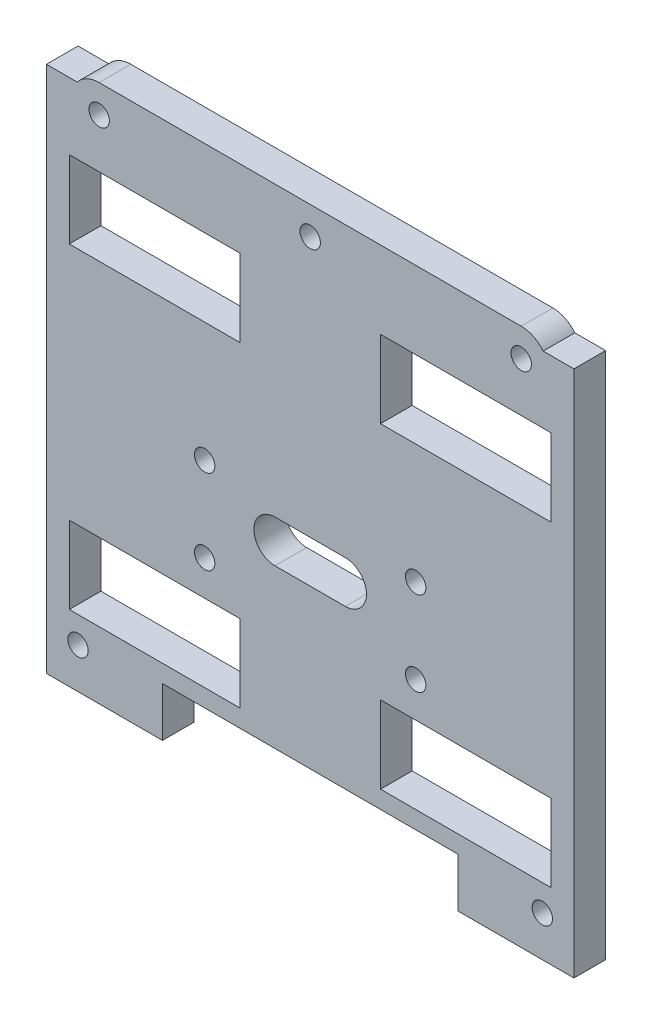
SolidWorks part; units mm, degrees
ref_plane "Front Plane" through (0, 0, 0) normal (0, 0, 1) x (1, 0, 0)
ref_plane "Top Plane" through (0, 0, 0) normal (0, 1, 0) x (1, 0, 0)
ref_plane "Right Plane" through (0, 0, 0) normal (1, 0, 0) x (0, 0, -1)
sketch "Sketch1" plane through (0, 0, 0) normal (0, 0, 1) x (1, 0, 0)
  line L0 (0, -37.5) -> (0, 37.5) construction
  line L1 (-47.5, -37.5) -> (47.5, -37.5)
  line L2 (-47.5, -37.5) -> (-47.5, 37.5)
  line L3 (-47.5, 37.5) -> (47.5, 37.5)
  line L4 (47.5, -37.5) -> (47.5, 37.5)
  line L5 (-47.5, -37.5) -> (47.5, 37.5) construction
  line L6 (-47.5, 37.5) -> (47.5, -37.5) construction
  line L7 (-47.5, 0) -> (47.5, 0) construction
  line L8 (-47.5, 22.5) -> (47.5, 22.5) construction
  line L9 (34.25, 17) -> (10, 28) construction
  line L10 (-34.25, 28) -> (-10, 28)
  line L11 (-34.25, 28) -> (-34.25, 17)
  line L12 (-34.25, 17) -> (-10, 17)
  line L13 (-10, 28) -> (-10, 17)
  line L14 (-34.25, 28) -> (-10, 17) construction
  line L15 (-34.25, 17) -> (-10, 28) construction
  line L16 (34.25, 28) -> (10, 17) construction
  line L17 (10, 28) -> (10, 17)
  line L18 (34.25, 17) -> (10, 17)
  line L19 (34.25, 28) -> (34.25, 17)
  line L20 (34.25, 28) -> (10, 28)
  line L21 (34.25, -28) -> (10, -17) construction
  line L22 (-34.25, -17) -> (-10, -28) construction
  line L23 (-34.25, -28) -> (-10, -17) construction
  line L24 (34.25, -17) -> (10, -28) construction
  line L25 (34.25, -28) -> (10, -28)
  line L26 (34.25, -28) -> (34.25, -17)
  line L27 (34.25, -17) -> (10, -17)
  line L28 (10, -28) -> (10, -17)
  line L29 (-10, -28) -> (-10, -17)
  line L30 (-34.25, -17) -> (-10, -17)
  line L31 (-34.25, -28) -> (-34.25, -17)
  line L32 (-34.25, -28) -> (-10, -28)
  point P0 (0, 0)
  point P12 (-22.125, 22.5)
  point P21 (22.125, 22.5)
  point P30 (22.125, -22.5)
  point P31 (-22.125, -22.5)
  dimension "D1" = 95
  dimension "D2" = 75
  dimension "D3" = 22.5
  dimension "D4" = 24.25
  dimension "D5" = 11
  dimension "D6" = 10
extrude "Boss-Extrude1" add sketch "Sketch1" along normal blind 4.5
sketch "Sketch8" plane through (0, 0, 4.5) normal (0, 0, 1) x (1, 0, 0)
  line L0 (-47.5, 37.5) -> (-47.5, -37.5) construction
  line L1 (47.5, -37.5) -> (47.5, 37.5) construction
  circle A0 centre (-47.5, 29.5) radius 8
  circle A1 centre (47.5, 29.5) radius 8
  dimension "D1" = 16
extrude "Boss-Extrude2" [suppressed] add sketch "Sketch8" against normal through all
sketch "Sketch2" plane through (0, 0, 4.5) normal (0, 0, 1) x (1, 0, 0)
  line L0 (0, -37.5) -> (0, 37.5) construction
  line L1 (-47.5, -37.5) -> (47.5, -37.5) construction
  line L2 (47.5, 37.5) -> (-47.5, 37.5) construction
  line L3 (-47.5, 0) -> (47.5, 0) construction
  line L4 (-47.5, 37.5) -> (-47.5, -37.5) construction
  line L5 (47.5, -37.5) -> (47.5, 37.5) construction
  line L6 (-40, 0) -> (40, 0) construction
  line L7 (-30, 35) -> (30, 35) construction
  circle A0 centre (-30, 35) radius 1.45
  circle A1 centre (30, 35) radius 1.45
  circle A2 centre (40, 0) radius 1.45
  circle A3 centre (-40, 0) radius 1.45
  circle A4 centre (0, 35) radius 1.45
  dimension "D1" = 2.9
  dimension "D7" = 2.9
  dimension "D8" = 2.9
  dimension "D9" = 2.9
  dimension "D2" = 30
  dimension "D3" = 35
  dimension "D4" = 80
  dimension "D5" = 40
  dimension "D6" = 0
extrude "screwHoles" cut sketch "Sketch2" against normal through all
sketch "Sketch3" plane through (0, 0, 4.5) normal (0, 0, 1) x (1, 0, 0)
  line L0 (-47.5, -20) -> (26.0486, -20) construction
  line L1 (-47.5, 37.5) -> (-47.5, -37.5) construction
  line L3 (0, 37.5) -> (0, -37.5) construction
  line L4 (47.5, 37.5) -> (-47.5, 37.5) construction
  line L5 (-47.5, -37.5) -> (47.5, -37.5) construction
  line L6 (18.95, -22.2) -> (9.05, -17.8) construction
  line L7 (-18.95, -17.8) -> (-9.05, -17.8)
  line L8 (-18.95, -17.8) -> (-18.95, -22.2)
  line L9 (-18.95, -22.2) -> (-9.05, -22.2)
  line L10 (-9.05, -17.8) -> (-9.05, -22.2)
  line L11 (-18.95, -17.8) -> (-9.05, -22.2) construction
  line L12 (-18.95, -22.2) -> (-9.05, -17.8) construction
  line L13 (18.95, -17.8) -> (9.05, -22.2) construction
  line L14 (9.05, -17.8) -> (9.05, -22.2)
  line L15 (18.95, -22.2) -> (9.05, -22.2)
  line L16 (18.95, -17.8) -> (18.95, -22.2)
  line L17 (18.95, -17.8) -> (9.05, -17.8)
  line L18 (-47.5, 37.5) -> (-47.5, -37.5) construction
  point P2 (-47.5, 0)
  point P12 (-14, -20)
  point P21 (14, -20)
  dimension "D1" = 9.9
  dimension "D3" = 14
  dimension "D4" = 20
extrude "BeltClamp" [suppressed] cut sketch "Sketch3" against normal through all
sketch "Sketch4" plane through (0, 0, 4.5) normal (0, 0, 1) x (1, 0, 0)
  line L0 (-47.5, 0) -> (47.5, 0) construction
  line L1 (-47.5, 37.5) -> (-47.5, -37.5) construction
  line L2 (47.5, -37.5) -> (47.5, 37.5) construction
  line L3 (0, 0) -> (0, 33.55) construction
  line L4 (-29.85, 2.175) -> (-20.15, 2.175)
  line L5 (-29.85, 2.175) -> (-29.85, -2.175)
  line L6 (-29.85, -2.175) -> (-20.15, -2.175)
  line L7 (-20.15, 2.175) -> (-20.15, -2.175)
  line L8 (-29.85, 2.175) -> (-20.15, -2.175) construction
  line L9 (-29.85, -2.175) -> (-20.15, 2.175) construction
  line L10 (29.85, -2.175) -> (20.15, 2.175) construction
  line L11 (29.85, 2.175) -> (20.15, -2.175) construction
  line L12 (20.15, 2.175) -> (20.15, -2.175)
  line L13 (29.85, -2.175) -> (20.15, -2.175)
  line L14 (29.85, 2.175) -> (29.85, -2.175)
  line L15 (29.85, 2.175) -> (20.15, 2.175)
  line L16 (-29.85, -2.175) -> (-20.15, 2.175) construction
  circle A0 centre (-40, 0) radius 1.45 construction
  circle A1 centre (0, 35) radius 1.45 construction
  point P6 (-25, 0)
  point P22 (25, 0)
  dimension "D3" = 0
  dimension "D2" = 4.35
  dimension "D4" = 25
extrude "Cut-Extrude3" [suppressed] cut sketch "Sketch4" against normal through all
sketch "Sketch5" plane through (0, 0, 4.5) normal (0, 0, 1) x (1, 0, 0)
  line L0 (-47.5, -9.75) -> (47.5, -9.75) construction
  line L1 (-47.5, 37.5) -> (-47.5, -37.5) construction
  line L2 (47.5, -37.5) -> (47.5, 37.5) construction
  line L4 (0, -37.5) -> (0, 37.5) construction
  line L5 (-47.5, -37.5) -> (47.5, -37.5) construction
  line L6 (47.5, 37.5) -> (-47.5, 37.5) construction
  line L7 (-30.825, -14.6) -> (-35.175, -4.9) construction
  line L8 (30.825, -4.9) -> (35.175, -4.9)
  line L9 (30.825, -4.9) -> (30.825, -14.6)
  line L10 (30.825, -14.6) -> (35.175, -14.6)
  line L11 (35.175, -4.9) -> (35.175, -14.6)
  line L12 (30.825, -4.9) -> (35.175, -14.6) construction
  line L13 (30.825, -14.6) -> (35.175, -4.9) construction
  line L14 (-30.825, -4.9) -> (-35.175, -14.6) construction
  line L15 (-35.175, -4.9) -> (-35.175, -14.6)
  line L16 (-30.825, -14.6) -> (-35.175, -14.6)
  line L17 (-30.825, -4.9) -> (-30.825, -14.6)
  line L18 (-30.825, -4.9) -> (-35.175, -4.9)
  line L19 (33, -9.75) -> (33, -37.5) construction
  line L20 (-33, -9.75) -> (-33, -37.5) construction
  line L21 (-33, -31.75) -> (33, -31.75) construction
  circle A0 centre (33, -31.75) radius 1.45
  circle A1 centre (-33, -31.75) radius 1.45
  point P15 (33, -9.75)
  point P24 (-33, -9.75)
  dimension "D5" = 2.9
  dimension "D2" = 9.7
  dimension "D3" = 4.35
  dimension "D4" = 33
  dimension "D6" = 22
  dimension "D1" = 9.75
extrude "Cut-Extrude4" [suppressed] cut sketch "Sketch5" against normal through all
sketch "Sketch9" plane through (0, 0, 4.5) normal (0, 0, 1) x (1, 0, 0)
  line L0 (47.5, 37.5) -> (-47.5, 37.5) construction
  line L1 (0, 37.5) -> (0, -37.5) construction
  line L2 (-47.5, -37.5) -> (47.5, -37.5) construction
  line L3 (50.5, 35) -> (45.5, 35) construction
  line L4 (-50.5, 35) -> (-45.5, 35) construction
  circle A0 centre (-30, 35) radius 4
  circle A1 centre (-30, 35) radius 1.45
  circle A2 centre (-30, 35) radius 1.45 construction
  circle A3 centre (30, 35) radius 1.45
  circle A4 centre (30, 35) radius 4
  point P17 (0, -37.5)
  dimension "D1" = 8
extrude "Boss-Extrude3" add sketch "Sketch9" against normal through all
sketch "Sketch10" plane through (0, 0, 4.5) normal (0, 0, 1) x (1, 0, 0)
  line L0 (-60, 37.5) -> (-37.5, 37.5)
  line L1 (-37.5, 37.5) -> (-37.5, -37.5)
  line L2 (-47.5, -37.5) -> (47.5, -37.5) construction
  line L3 (-37.5, -37.5) -> (-60, -37.5)
  line L4 (-60, -37.5) -> (-60, 37.5)
  line L5 (0, 37.5) -> (0, -37.5) construction
  line L6 (26.8775, 37.5) -> (-26.8775, 37.5) construction
  line L7 (60, -37.5) -> (60, 37.5)
  line L8 (37.5, -37.5) -> (60, -37.5)
  line L9 (37.5, 37.5) -> (37.5, -37.5)
  line L10 (60, 37.5) -> (37.5, 37.5)
  line L11 (-60, -37.5) -> (-60, 37.5)
  line L12 (-33.1225, 37.5) -> (-47.5, 37.5) construction
  line M3 (47.5, -37.5) -> (47.5, 37.5)
  line M7 (-47.5, 37.5) -> (-47.5, -37.5)
  line M8 (-47.5, -37.5) -> (47.5, -37.5)
  dimension "D3" = 0
  dimension "D1" = 75
  dimension "D2" = 60
extrude "Cut-Extrude5" cut sketch "Sketch10" against normal through all contours L1 L0 M7 M8 | L10 L9 M3 M8 region at (42.5, 0, 4.5) region at (-42.5, 0, 4.5)
sketch "Sketch11" plane through (0, 0, 4.5) normal (0, 0, 1) x (1, 0, 0)
  line L0 (-30, 39) -> (30, 39)
  line L1 (30, 39) -> (26.8775, 37.5)
  line L2 (26.8775, 37.5) -> (-26.8775, 37.5)
  line L3 (-26.8775, 37.5) -> (-30, 39)
  arc A0 (-26.8775, 37.5) -> (-33.1225, 37.5) centre (-30, 35) ccw construction
  arc A1 (33.1225, 37.5) -> (26.8775, 37.5) centre (30, 35) ccw construction
extrude "Boss-Extrude4" add sketch "Sketch11" against normal through all
sketch "Sketch12" plane through (0, 0, 4.5) normal (0, 0, 1) x (1, 0, 0)
  line L0 (-37.5, -12) -> (37.5, -12) construction
  line L1 (-37.5, 37.5) -> (-37.5, -37.5) construction
  line L2 (37.5, 37.5) -> (37.5, -37.5) construction
  line L3 (0, 0) -> (0, -37.5) construction
  line L4 (-37.5, -37.5) -> (37.5, -37.5) construction
  circle A0 centre (-15, -12) radius 1.45
  circle A1 centre (15, -12) radius 1.45
  dimension "D2" = 2.9
  dimension "D1" = 15
  dimension "D3" = 12
extrude "FanBraceScrews" cut sketch "Sketch12" against normal through all
sketch "Sketch13" plane through (0, 0, 4.5) normal (0, 0, 1) x (1, 0, 0)
  line L0 (-37.5, -37.5) -> (37.5, -37.5) construction
  line L1 (-21, -44.5) -> (21, -44.5)
  line L2 (-21, -44.5) -> (-21, -30.5)
  line L3 (-21, -30.5) -> (21, -30.5)
  line L4 (21, -44.5) -> (21, -30.5)
  line L5 (-21, -44.5) -> (21, -30.5) construction
  line L6 (-21, -30.5) -> (21, -44.5) construction
  point P0 (0, -37.5)
  dimension "D1" = 42
  dimension "D2" = 7
extrude "Cut-Extrude7" cut sketch "Sketch13" against normal through all
sketch "Sketch20" plane through (0, 0, 0) normal (0, 0, -1) x (-1, 0, 0)
  line L0 (15, -10.55) -> (15, 0) construction
  line L1 (0, 0) -> (0, 8.2059) construction
  line L2 (-15, -10.55) -> (-15, 0) construction
  circle A0 centre (15, -12) radius 1.45 construction
  circle A1 centre (15, 0) radius 1.45
  circle A2 centre (-15, 0) radius 1.45
  dimension "D1" = 12
extrude "Cut-Extrude11" cut sketch "Sketch20" against normal through all
sketch "Sketch14" plane through (0, 0, 4.5) normal (0, 0, 1) x (1, 0, 0)
  line L0 (15, -13.45) -> (15, 0) construction
  line L1 (0, 0) -> (0, -40.3958) construction
  line L2 (-15, -13.45) -> (-15, 0) construction
  circle A0 centre (15, -12) radius 1.45 construction
  circle A1 centre (15, 0) radius 1.45
  circle A2 centre (-15, 0) radius 1.45
  dimension "D2" = 2.9
  dimension "D1" = 12
extrude "Cut-Extrude8" [suppressed] cut sketch "Sketch14" against normal through all
sketch "Sketch15" plane through (0, 0, 4.5) normal (0, 0, 1) x (1, 0, 0)
  line L0 (-25, 1.5) -> (-25, -10.5) construction
  line L2 (0, 0) -> (0, -11.0705) construction
  line L3 (16, -8.3509) -> (25, -10.5) construction
  line L4 (25, 1.5) -> (25, -10.5) construction
  circle A0 centre (-25, 1.5) radius 1.45
  circle A1 centre (-25, -10.5) radius 1.45
  circle A2 centre (25, -10.5) radius 1.45
  circle A3 centre (25, 1.5) radius 1.45
  circle A5 centre (-15, -12) radius 1.45 construction
  dimension "D1" = 12
  dimension "D3" = 2.9
  dimension "D4" = 2.9
  dimension "D2" = 25
  dimension "D5" = 1.5
extrude "BeltClipScrews" [suppressed] cut sketch "Sketch15" against normal through all
sketch "Sketch16" [suppressed] plane through (0, 0, 4.5) normal (0, 0, 1) x (1, 0, 0)
  line L0 (0, 0) -> (0, -11.3016) construction
  line L1 (-29.85, 2.175) -> (-20.15, 2.175)
  line L2 (-29.85, 2.175) -> (-29.85, -2.175)
  line L3 (-29.85, -2.175) -> (-20.15, -2.175)
  line L4 (-20.15, 2.175) -> (-20.15, -2.175)
  line L5 (-35.175, -4.9) -> (-30.825, -4.9)
  line L6 (-35.175, -4.9) -> (-35.175, -14.6)
  line L7 (-35.175, -14.6) -> (-30.825, -14.6)
  line L8 (-30.825, -4.9) -> (-30.825, -14.6)
  line L9 (30.825, -4.9) -> (30.825, -14.6)
  line L10 (35.175, -14.6) -> (30.825, -14.6)
  line L11 (35.175, -4.9) -> (35.175, -14.6)
  line L12 (35.175, -4.9) -> (30.825, -4.9)
  line L13 (20.15, 2.175) -> (20.15, -2.175)
  line L14 (29.85, -2.175) -> (20.15, -2.175)
  line L15 (29.85, 2.175) -> (29.85, -2.175)
  line L16 (29.85, 2.175) -> (20.15, 2.175)
  line L17 (-30.825, -4.9) -> (-30.825, -14.6)
extrude "Boss-Extrude5" [suppressed] add sketch "Sketch16" against normal through all contours L8 L5 L6 L7 | L4 L1 L2 L3 | L15 L16 L13 L14 | L11 L12 L9 L10
sketch "Sketch17" [suppressed] plane through (0, 0, 4.5) normal (0, 0, 1) x (1, 0, 0)
  line L0 (0, -30.5) -> (0, 0) construction
  line L1 (21, -30.5) -> (-21, -30.5) construction
  line L2 (-37.5, -37.5) -> (-46.5, -37.5)
  line L3 (-46.5, -37.5) -> (-46.5, -22.5)
  line L4 (-46.5, -22.5) -> (-43.5, -22.5)
  line L5 (-43.5, -22.5) -> (-43.5, -32.5)
  line L6 (-43.5, -32.5) -> (-37.5, -32.5)
  line L7 (-37.5, 37.5) -> (-37.5, -37.5) construction
  line L8 (-37.5, -32.5) -> (-37.5, -37.5)
  line L9 (-37.5, -37.5) -> (-37.5303, -37.4889)
  dimension "D1" = 3
  dimension "D2" = 6
  dimension "D3" = 5
  dimension "D4" = 15
extrude "Boss-Extrude6" [suppressed] add sketch "Sketch17" against normal through all contours L8 L6 L5 L4 L3 L2
sketch "Sketch18" plane through (0, 0, 0) normal (0, 0, 1) x (1, 0, 0)
  line L0 (0, -30.5) -> (0, 0) construction
  line L1 (-37.5, -37.5) -> (-21, -37.5) construction
  line L7 (-37.5, -27.5) -> (-37.5, -22.5)
  line L9 (-43.5, -27.5) -> (-37.5, -27.5)
  line L10 (-37.5, -30) -> (-45.5, -30) construction
  line L11 (-37.5, 37.5) -> (-37.5, -37.5) construction
  line L12 (-43.5, -37.5) -> (-43.5, -27.5)
  line L13 (-46.5, -37.5) -> (-43.5, -37.5)
  line L14 (-46.5, -22.5) -> (-46.5, -37.5)
  line L15 (-37.5, -22.5) -> (-46.5, -22.5)
  dimension "D1" = 6
  dimension "D2" = 15
  dimension "D3" = 5
extrude "Boss-Extrude7" [suppressed] add sketch "Sketch18" along normal through all
mirror "Mirror1" [suppressed] about plane through (0, 0, 0) normal (1, 0, 0)
fillet "Fillet1" [suppressed] radius 2
mirror "Mirror2" [suppressed] about plane through (0, 0, 0) normal (1, 0, 0)
fillet "Fillet2" [suppressed] radius 2
sketch "Sketch19" plane through (0, 0, 4.5) normal (0, 0, 1) x (1, 0, 0)
  line L0 (-5, -5) -> (5, -5) construction
  line L1 (-5, -2) -> (5, -2)
  line L2 (-5, -8) -> (5, -8)
  line L3 (0, 0) -> (0, -15.8058) construction
  arc A0 (-5, -2) -> (-5, -8) centre (-5, -5) ccw
  arc A1 (5, -8) -> (5, -2) centre (5, -5) ccw
  point P2 (0, -5)
  dimension "D1" = 10
  dimension "D2" = 6
  dimension "D3" = 0
  dimension "D4" = 5
extrude "Cut-Extrude9" cut sketch "Sketch19" against normal through all
sketch "Sketch21" plane through (0, 0, 0) normal (0, 0, -1) x (-1, 0, 0)
  line L0 (0, 0) -> (0, -30.5) construction
  line L1 (-21, -30.5) -> (21, -30.5) construction
  circle A0 centre (-33, -31.75) radius 1.45
  circle A1 centre (33, -31.75) radius 1.45
  dimension "D1" = 2.9
  dimension "D2" = 33
  dimension "D3" = 31.75
extrude "Cut-Extrude12" cut sketch "Sketch21" against normal through all
equation "\"X-ROD-SPACING\"=45"
equation "\"Y-ROD-SPACING\"=75"
equation "\"Z-ROD-SPACING\"=17.5"
equation "\"Y-BED-OFFSET\"=2"
equation "\"Y-BED-ROD-INSET\"=3.5"
equation "\"Y-BED-SCREW-SPACING\"=209"
equation "\"Y-BED-SCREW-CUTOUT-SLOT-HEIGHT\"=2"
equation "\"T-SLOT-NUT-FILLET-RADIUS\"=0.5"
equation "\"T-SLOT-SCREW-SHAFT-RADIUS\"=1.55"
equation "\"T-SLOT-SCREW-SHAFT-CUTOUT-LENGTH\"=11"
equation "\"T-SLOT-NUT-DEPTH\"=3.5"
equation "\"T-SLOT-NUT-WIDTH\"=2.85"
equation "\"T-SLOT-NUT-END-DISTANCE\"=8"
equation "\"ACRYLIC-THICKNESS\"=10"
equation "\"ACRYLIC-THICKNESS2\"=4.5"
equation "\"ACRYLIC-TAB-CUTOUT-SIZE\"=\"ACRYLIC-THICKNESS\"+\"ACRYLIC-TAB-TOLERANCE\"*2"
equation "\"ACRYLIC-TAB-WIDTH\"=\"ACRYLIC-THICKNESS\""
equation "\"ACRYLIC-M3-HOLE\"=2.9"
equation "\"SMOOTHROD-CAP-SCREW-DISTANCE\"=20"
equation "\"FRAME-WIDTH-INNER\"=370"
equation "\"NEMA17-HOLE-SPACING\"=31"
equation "\"NEMA17-CENTRAL-CUTOUT\"=22.5"
equation "\"Z-BRACKET-REACH\"=57"
equation "\"Z-ROD-INSET\"=13.5"
equation "\"TOP-BRACKET-SPACING\"=40"
equation "\"SMOOTHROD-X-LENGTH\"=350"
equation "\"SMOOTHROD-Y-LENGTH\"=350"
equation "\"SMOOTHROD-Z-LENGTH\"=350"
equation "\"SMOOTHROD-TIGHTENING-HEADROOM\"=.25"
equation "\"LEADSCREW-Z-LENGTH\"=300"
equation "\"SCREW-LENGTH-FRAME\"=\"ACRYLIC-THICKNESS\" + 10"
equation "\"SCREW-LENGTH-MOTOR\"=\"ACRYLIC-THICKNESS\" + 5"
equation "\"SCREW-HEAD-RADIUS\"=6"
equation "\"PRINTED-X-SMOOTHROD-DIAMETER\"=8.8"
equation "\"PRINTED-X-SMOOTHROD-CUTOUT\"=10"
equation "\"PRINTED-X-BASE-HEIGHT\"=10"
equation "\"PRINTED-LM8UU-CUTOUT-SIZE\"=15.5"
equation "\"PRINTED-LM8UU-CUTOUT-LENGTH\"=24.5"
equation "\"PRINTED-X-IDLER-HEIGHT\"=16"
equation "\"PSU-MOUNTING-WIDTH\"=95"
equation "\"PSU-MOUNTING-HEIGHT\"=177"
equation "\"Y-BELT-TO-ROD-DISTANCE\"=20"
equation "\"SPOOL-HOLDER-ROD-SPACING\"=150"
equation "\"D3@Sketch1\"=\"X-ROD-SPACING\"/2"
equation "\"D4@Sketch1\"=\"ACRYLIC-X-CARRIAGE-LM8UU-CUTOUT-WIDTH\""
equation "\"D1@Boss-Extrude1\"=\"ACRYLIC-THICKNESS2\""
equation "\"D1@Sketch2\"=\"ACRYLIC-M3-HOLE\""
equation "\"D1@Sketch3\"=\"ACRYLIC-TAB-CUTOUT-SIZE\""
equation "\"D2@Sketch3\"=\"ACRYLIC-THICKNESS2\"+\"ACRYLIC-TAB-TOLERANCE\"*2"
equation "\"ACRYLIC-X-CARRIAGE-WIDTH\"=55"
equation "\"ACRYLIC-X-CARRIAGE-HEIGHT\"=75"
equation "\"D2@Sketch1\"=\"ACRYLIC-X-CARRIAGE-HEIGHT\""
equation "\"ACRYLIC-X-CARRIAGE-CENTER-TAB-SPACING\"=14"
equation "\"D3@Sketch3\"=\"ACRYLIC-X-CARRIAGE-CENTER-TAB-SPACING\""
equation "\"SCREW-LENGTH-EXTRUDER\"=28"
equation "\"ACRYLIC-X-CARRIAGE-SCREW-SPACING-X\"=15"
equation "\"ACRYLIC-X-CARRIAGE-SCREW-SPACING-Y\"=33"
equation "\"D1@Sketch4\"=\"ACRYLIC-TAB-WIDTH\"-\"KERF\"*4"
equation "\"D2@Sketch4\"=\"ACRYLIC-THICKNESS2\"-\"KERF\"*2"
equation "\"D2@Sketch5\"=\"ACRYLIC-TAB-WIDTH\"-\"KERF\"*4"
equation "\"D3@Sketch5\"=\"ACRYLIC-THICKNESS2\"-\"KERF\"*2"
equation "\"ACRYLIC-X-CARRIAGE-EXTRUDER-SHELF-DEPTH\"=\"ACRYLIC-X-CARRIAGE-EXTRUDER-OFFSET\" + 28"
equation "\"ACRYLIC-X-CARRIAGE-EXTRUDER-BRACE-SPACING\"=23"
equation "\"D4@Sketch5\"=\"ACRYLIC-X-CARRIAGE-DUAL-MOUNT-BRACE-WIDTH\""
equation "\"D1@Sketch5\"=\"ACRYLIC-THICKNESS2\"/2 + 7.5"
equation "\"D4@Sketch2\"=\"ACRYLIC-X-CARRIAGE-DUAL-MOUNT-SCREW-WIDTH\"*2"
equation "\"D5@Sketch2\"=\"ACRYLIC-X-CARRIAGE-DUAL-MOUNT-SCREW-WIDTH\""
equation "\"D7@Sketch2\"=\"ACRYLIC-M3-HOLE\""
equation "\"D8@Sketch2\"=\"ACRYLIC-M3-HOLE\""
equation "\"ACRYLIC-X-CARRIAGE-LM8UU-CUTOUT-WIDTH\"=24.25"
equation "\"ACRYLIC-TAB-TOLERANCE\"=-.05"
equation "\"ACRYLIC-X-CARRIAGE-EXTRUDER-OFFSET\"=26"
equation "\"ACRYLIC-X-CARRIAGE-EXTRUDER-ANGLE\"=90"
equation "\"ACRYLIC-X-CARRIAGE-EXTRUDER-BRACE-TAB-OFFSET\"=20"
equation "\"ACRYLIC-X-CARRIAGE-EXTRUDER-BRACE-HEIGHT\"=35"
equation "\"ACRYLIC-X-CARRIAGE-EXTRUDER-BRACE-SCREW-SPACING\"=22"
equation "\"D5@Sketch5\"=\"ACRYLIC-M3-HOLE\""
equation "\"ACRYLIC-X-CARRIAGE-DUAL-WIDTH-MULTIPLIER\"=1.65"
equation "\"ACRYLIC-X-CARRIAGE-DUAL-HOTEND-SPACING\"=42"
equation "\"ACRYLIC-X-CARRIAGE-DUAL-WIDTH\"=75"
equation "\"ACRYLIC-X-CARRIAGE-DUAL-HOTEND-SEPARATION\"=36"
equation "\"ACRYLIC-X-CARRIAGE-DUAL-MOUNT-PLATE-DEPTH\"=75"
equation "\"ACRYLIC-X-CARRIAGE-DUAL-MOUNT-BRACE-WIDTH\"=33"
equation "\"ACRYLIC-X-CARRIAGE-DUAL-MOUNT-SCREW-WIDTH\"=40"
equation "\"D9@Sketch2\"=\"ACRYLIC-M3-HOLE\""
equation "\"ACRYLIC-X-CARRIAGE-LM8UU-CUTOUT-HEIGHT\"=11.0"
equation "\"D5@Sketch1\"=\"ACRYLIC-X-CARRIAGE-LM8UU-CUTOUT-HEIGHT\""
equation "\"D1@Sketch10\"=\"ACRYLIC-X-CARRIAGE-DUAL-WIDTH\""
equation "\"D2@Sketch12\"=\"ACRYLIC-M3-HOLE\""
equation "\"D2@Sketch14\"=\"ACRYLIC-M3-HOLE\""
equation "\"D3@Sketch15\"=\"ACRYLIC-M3-HOLE\""
equation "\"D4@Sketch15\"=\"ACRYLIC-M3-HOLE\""
equation "\"KERF\"=0.075"
equation "\"ACRYLIC-THICKNESS-TAB-CUTOUT-WIDTH\"=\"ACRYLIC-THICKNESS\"-\"KERF\"*2"
equation "\"ACRYLIC-THICKNESS-TAB-CUTOUT-HEIGHT\"=\"ACRYLIC-TAB-WIDTH\"-\"KERF\"*4"
equation "\"ACRYLIC-THICKNESS2-TAB-CUTOUT-WIDTH\"=\"ACRYLIC-THICKNESS2\"-\"KERF\"*2"
equation "\"ACRYLIC-THICKNESS2-TAB-CUTOUT-HEIGHT\"=\"ACRYLIC-TAB-WIDTH\"-\"KERF\"*4"
equation "\"PRINTED-M3-HOLE\"=3.5"
equation "\"PRINTED-M3-NUT-AF\"=6.25"
equation "\"ACRYLIC-X-CARRIAGE-DUAL-FAN-OFFSET\"=52"
equation "\"ACRYLIC-X-CARRIAGE-DUAL-FAN-HEIGHT\"=20"
equation "\"BLOWER-FAN-WIDTH\"=15"
equation "\"D1@Sketch21\"=\"ACRYLIC-M3-HOLE\""
equation "\"D2@Sketch21\"=\"ACRYLIC-X-CARRIAGE-DUAL-MOUNT-BRACE-WIDTH\""
equation "\"D3@Sketch21\"=\"ACRYLIC-THICKNESS2\"/2 + 7.5+22"
